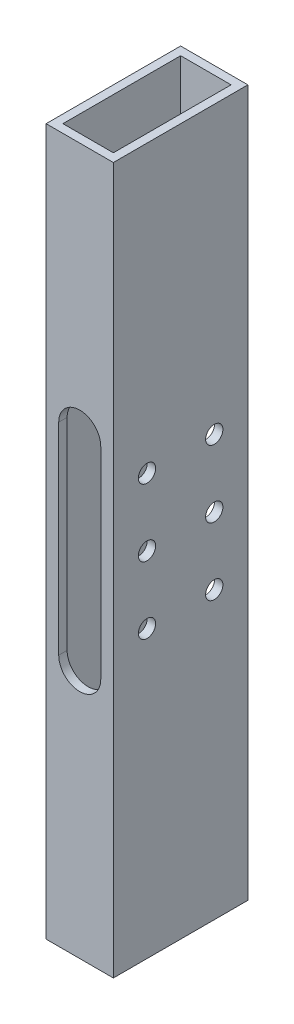
SolidWorks part; units mm, degrees
ref_plane "Front Plane" through (0, 0, 0) normal (0, 0, 1) x (1, 0, 0)
ref_plane "Top Plane" through (0, 0, 0) normal (0, 1, 0) x (1, 0, 0)
ref_plane "Right Plane" through (0, 0, 0) normal (1, 0, 0) x (0, 0, -1)
sketch "Sketch1" plane through (0, 0, 0) normal (0, 1, 0) x (1, 0, 0)
  line L0 (-9.525, 22.225) -> (9.525, 22.225)
  line L1 (-12.7, -25.4) -> (12.7, -25.4)
  line L2 (-12.7, -25.4) -> (-12.7, 25.4)
  line L3 (-12.7, 25.4) -> (12.7, 25.4)
  line L4 (12.7, -25.4) -> (12.7, 25.4)
  line L5 (-12.7, -25.4) -> (12.7, 25.4) construction
  line L6 (-12.7, 25.4) -> (12.7, -25.4) construction
  line L7 (9.525, -22.225) -> (9.525, 22.225)
  line L8 (-9.525, -22.225) -> (9.525, -22.225)
  line L9 (-9.525, -22.225) -> (-9.525, 22.225)
  point P0 (0, 0)
  dimension "D1" = 25.4
  dimension "D2" = 50.8
  dimension "D3" = 3.175
extrude "Boss-Extrude1" add sketch "Sketch1" along normal blind 266.7
sketch "Sketch2" plane through (12.7, 0, 0) normal (1, 0, 0) x (0, 0, -1)
  line L0 (-25.4, 133.35) -> (25.4, 133.35) construction
  line L1 (-25.4, 266.7) -> (-25.4, 0) construction
  line L2 (25.4, 266.7) -> (25.4, 0) construction
  line L4 (-25.4, 171.45) -> (25.4, 171.45) construction
  line L5 (-25.4, 171.45) -> (-25.4, 95.25) construction
  line L6 (-25.4, 95.25) -> (25.4, 95.25) construction
  line L7 (25.4, 171.45) -> (25.4, 95.25) construction
  line L8 (-25.4, 171.45) -> (25.4, 95.25) construction
  line L9 (-25.4, 95.25) -> (25.4, 171.45) construction
  circle A0 centre (-12.7, 158.75) radius 3.2639
  circle A1 centre (12.7, 158.75) radius 3.2639
  circle A2 centre (12.7, 133.35) radius 3.2639
  circle A3 centre (12.7, 107.95) radius 3.2639
  circle A4 centre (-12.7, 133.35) radius 3.2639
  circle A5 centre (-12.7, 107.95) radius 3.2639
  point P6 (0, 133.35)
  point P13 (0, 0)
  point P14 (0, 0)
  point P15 (-10.0078, 154.3505)
  dimension "D4" = 6.5278
  dimension "D1" = 76.2
  dimension "D2" = 12.7
  dimension "D3" = 12.7
  dimension "D7" = 25.4
  dimension "D8" = 25.4
  dimension "D9" = 35.921
  dimension "D5" = 2
  dimension "D6" = 3
extrude "Cut-Extrude1" cut sketch "Sketch2" against normal blind 3.175
sketch "Sketch3" plane through (0, 0, 25.4) normal (0, 0, 1) x (1, 0, 0)
  line L0 (-12.7, 133.35) -> (12.7, 133.35) construction
  line L1 (-12.7, 266.7) -> (-12.7, 0) construction
  line L2 (12.7, 266.7) -> (12.7, 0) construction
  line L3 (0, 95.25) -> (0, 171.45) construction
  line L4 (-7.9375, 95.25) -> (-7.9375, 171.45)
  line L5 (7.9375, 95.25) -> (7.9375, 171.45)
  arc A0 (-7.9375, 95.25) -> (7.9375, 95.25) centre (0, 95.25) ccw
  arc A1 (7.9375, 171.45) -> (-7.9375, 171.45) centre (0, 171.45) ccw
  point P8 (0, 133.35)
  dimension "D1" = 76.2
  dimension "D2" = 15.875
extrude "Cut-Extrude2" cut sketch "Sketch3" against normal through all
